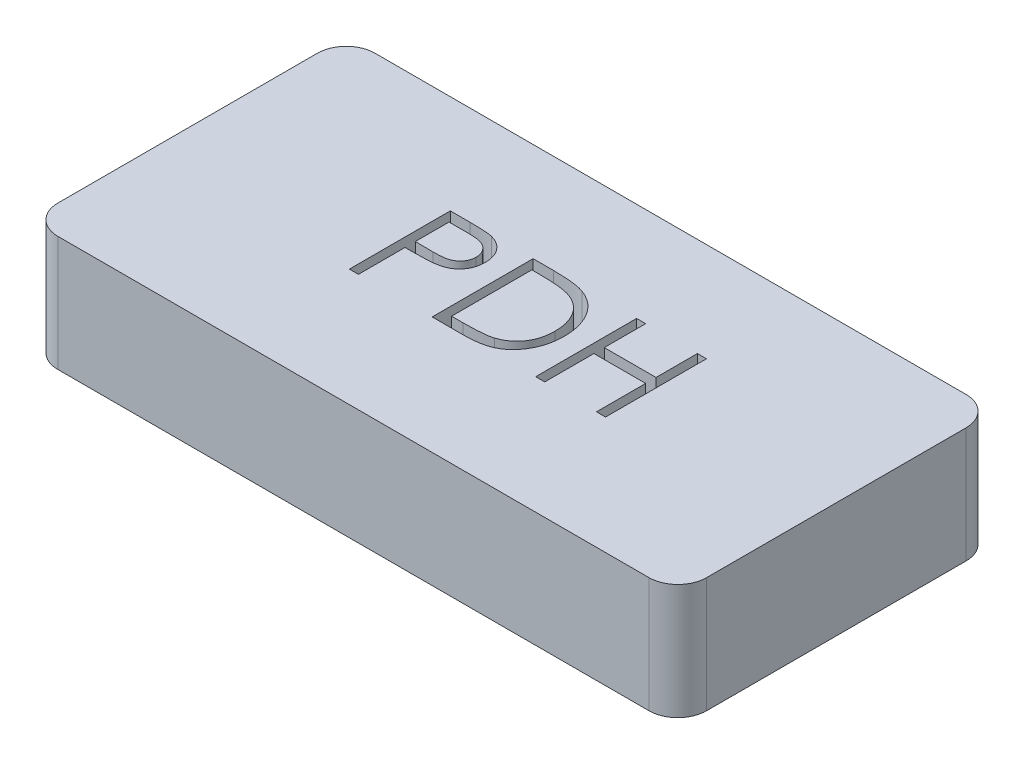
SolidWorks part; units mm, degrees
ref_plane "Front Plane" through (0, 0, 0) normal (0, 0, 1) x (1, 0, 0)
ref_plane "Top Plane" through (0, 0, 0) normal (0, 1, 0) x (1, 0, 0)
ref_plane "Right Plane" through (0, 0, 0) normal (1, 0, 0) x (0, 0, -1)
sketch "Sketch1" plane through (0, 0, 0) normal (0, 1, 0) x (1, 0, 0)
  line L1 (112.5, -55) -> (-112.5, -55)
  line L2 (112.5, -55) -> (112.5, 55)
  line L3 (112.5, 55) -> (-112.5, 55)
  line L4 (-112.5, -55) -> (-112.5, 55)
  line L5 (112.5, -55) -> (-112.5, 55) construction
  line L6 (112.5, 55) -> (-112.5, -55) construction
  point P0 (0, 0)
  dimension "D1" = 225
  dimension "D2" = 110
extrude "Boss-Extrude1" add sketch "Sketch1" along normal blind 40
fillet "Fillet1" radius 10 4 edges at (112.5, 20, -55) (112.5, 20, 55) (-112.5, 20, 55) (-112.5, 20, -55)
sketch "Sketch2" plane through (0, 40, 0) normal (0, 1, 0) x (1, 0, 0)
  text T0 "PDH\r\n" font "Century Gothic" height 35
  point P1 (0, 0)
  point P3 (0, -5.0739)
  point P4 (-53.5066, -3.2288)
  point P5 (-50.5084, -8.5334)
  point P6 (-46.5876, -14.2992)
  point P7 (0, 0)
  point P8 (0, 0)
extrude "Cut-Extrude1" cut sketch "Sketch2" against normal blind 40
